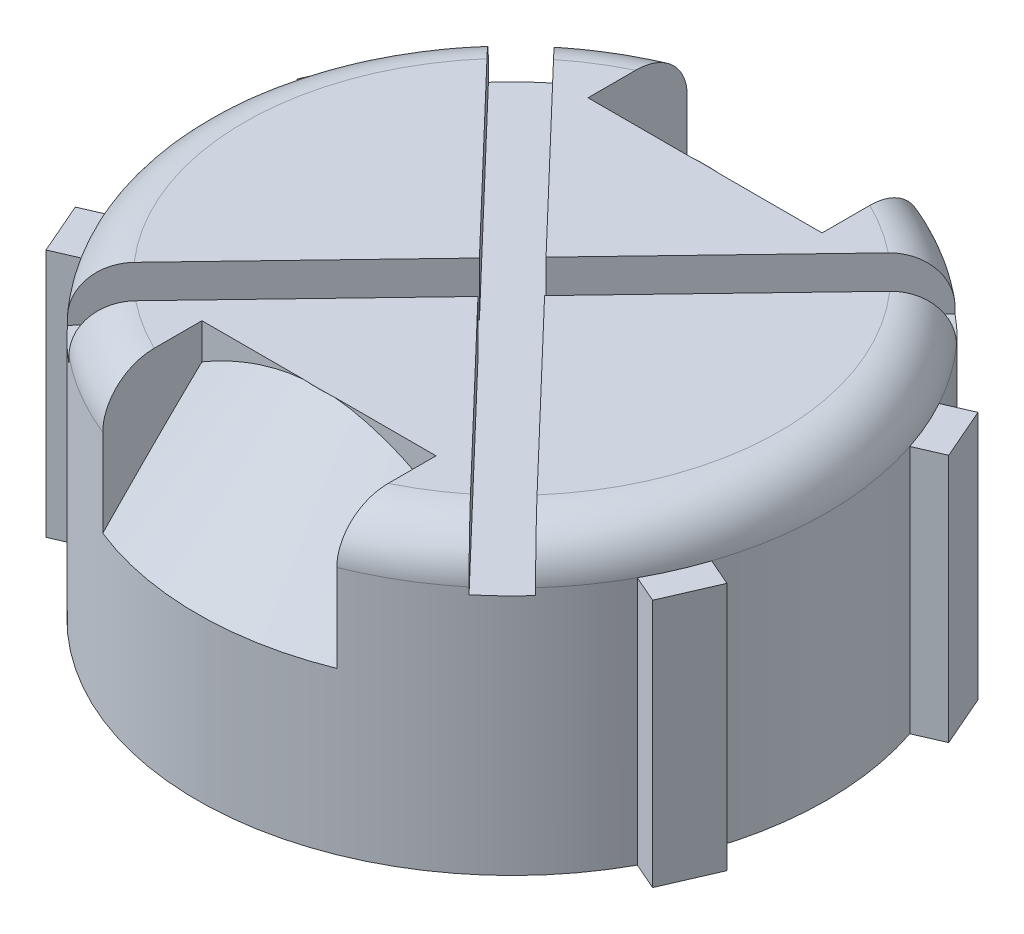
SolidWorks part; units mm, degrees
ref_plane "Front Plane" through (0, 0, 0) normal (0, 0, 1) x (1, 0, 0)
ref_plane "Top Plane" through (0, 0, 0) normal (0, 1, 0) x (1, 0, 0)
ref_plane "Right Plane" through (0, 0, 0) normal (1, 0, 0) x (0, 0, -1)
sketch "Sketch1" plane through (0, 0, 0) normal (0, 1, 0) x (1, 0, 0)
  circle A0 centre (0, 0) radius 11.7
extrude "Boss-Extrude1" add sketch "Sketch1" along normal blind 6 from offset 2 offset against normal yes
sketch "Sketch2" plane through (0, -2, 0) normal (0, -1, 0) x (1, 0, 0)
  circle A0 centre (0, 0) radius 11.7
  circle A1 centre (0, 0) radius 10.15
extrude "Boss-Extrude2" add sketch "Sketch2" along normal blind 5
sketch "Sketch7" plane through (0, 4, 0) normal (0, 1, 0) x (1, 0, 0)
  line L0 (11.2738, -6.047) -> (-12.1112, 4.1211)
  line L1 (11.2738, -6.047) -> (12.1112, -4.1211)
  line L2 (-12.1112, 4.1211) -> (-11.2738, 6.047)
  line L3 (12.1112, -4.1211) -> (-11.2738, 6.047)
  line L4 (-11.6925, 5.0841) -> (11.6925, -5.0841) construction
  line L5 (-0.4187, -0.9629) -> (0.4187, 0.9629) construction
  line L6 (-12.1112, -4.1211) -> (11.2738, 6.047)
  line L7 (-12.1112, -4.1211) -> (-11.2738, -6.047)
  line L8 (11.2738, 6.047) -> (12.1112, 4.1211)
  line L9 (-11.2738, -6.047) -> (12.1112, 4.1211)
  line L10 (11.6925, 5.0841) -> (-11.6925, -5.0841) construction
  line L11 (-0.4187, 0.9629) -> (0.4187, -0.9629) construction
  circle A0 centre (0, 0) radius 11.625
  point P1 (0, 0)
  point P3 (0, 0)
  circle M4 centre (0, 0) radius 11.7
  dimension "D1" = 2.1
  dimension "D2" = 25.5
  dimension "D3" = 25.5
  dimension "D4" = 2.1
extrude "Boss-Extrude3" add sketch "Sketch7" against normal up to surface (11 mm away) from offset 1.75 contours L3 L2 L0 M4 | L1 L3 L0 M4 | L7 L9 L6 M4 | L9 L8 L6 M4 region at (11.2038, 4, 4.8715) region at (-11.2038, 4, 4.8715) region at (-11.2038, 4, -4.8715) region at (11.2038, 4, -4.8715) up to face at (0, -7, -11.7) offset against normal yes
sketch "Sketch3" plane through (0, 4, 0) normal (0, 1, 0) x (1, 0, 0)
  line L0 (17.5201, -19.5671) -> (-18.7843, 18.357)
  line L1 (-11.0048, -10.2304) -> (9.7406, 11.4405)
  line L2 (-11.0048, -10.2304) -> (-9.7406, -11.4405)
  line L3 (-9.7406, -11.4405) -> (11.0048, 10.2304)
  line L4 (9.7406, 11.4405) -> (11.0048, 10.2304)
  line L5 (-11.0048, -10.2304) -> (11.0048, 10.2304) construction
  line L6 (-9.7406, -11.4405) -> (9.7406, 11.4405) construction
  line L7 (17.5201, -19.5671) -> (18.7843, -18.357)
  line L8 (-18.7843, 18.357) -> (-17.5201, 19.5671)
  line L9 (18.7843, -18.357) -> (-17.5201, 19.5671)
  line L10 (-18.1522, 18.9621) -> (18.1522, -18.9621) construction
  line L11 (-0.6321, -0.6051) -> (0.6321, 0.6051) construction
  point P0 (0, 0)
  point P5 (0, 0)
  point P7 (0, 0)
  circle M10 centre (0, 0) radius 11.7
  dimension "D1" = 1.75
  dimension "D2" = 1.75
extrude "Cut-Extrude1" cut sketch "Sketch3" against normal blind 2 contours L9 L3 L1 M10 | L9 L3 L0 M10 | L3 L9 L1 L0 | L1 L9 L0 M10 | L3 L0 L1 M10 region at (4.3451, 4, 4.5375) region at (-4.3451, 4, 4.5375) region at (0, 4, 0) region at (-4.3451, 4, -4.5375) region at (4.3451, 4, -4.5375)
sketch "Sketch6" plane through (0, 4, 0) normal (0, 1, 0) x (1, 0, 0)
  line L0 (10.25, 0) -> (-10.25, 0)
  line L1 (4.35, 16.225) -> (-4.35, 16.225)
  line L2 (4.35, 16.225) -> (4.35, 7.175)
  line L3 (4.35, 7.175) -> (-4.35, 7.175)
  line L4 (-4.35, 16.225) -> (-4.35, 7.175)
  line L5 (4.35, 16.225) -> (-4.35, 7.175) construction
  line L6 (4.35, 7.175) -> (-4.35, 16.225) construction
  line L7 (4.35, -16.225) -> (-4.35, -7.175) construction
  line L8 (-4.35, -16.225) -> (-4.35, -7.175)
  line L9 (4.35, -16.225) -> (-4.35, -16.225)
  line L10 (4.35, -7.175) -> (-4.35, -7.175)
  line L11 (4.35, -7.175) -> (-4.35, -16.225) construction
  line L12 (4.35, -16.225) -> (4.35, -7.175)
  point P0 (0, 11.7)
  point P5 (0, -11.7)
  arc M21 (-7.436, -9.0331) -> (7.436, -9.0331) centre (0, 0) ccw
  dimension "D1" = 8.7
  dimension "D2" = 9.05
extrude "Cut-Extrude3" cut sketch "Sketch6" against normal blind 0.0001 contours L1 L4 L3 L2 | L12 L10 L8 M21 region at (0, 4, -11.7) region at (0, 4, 9.3071)
chamfer "Chamfer1" distance 5 angle 42 2 edges at (0, 3.9999, -11.7) (0, 3.9999, 11.7) first distance on face at (0, -2.375, 0)
fillet "Fillet1" radius 1.75 6 edges at (-5.9635, 4, 10.0661) (5.9635, 4, 10.0661) (11.7, 4, 0) (5.9635, 4, -10.0661) (-5.9635, 4, -10.0661) (-11.7, 4, 0)
